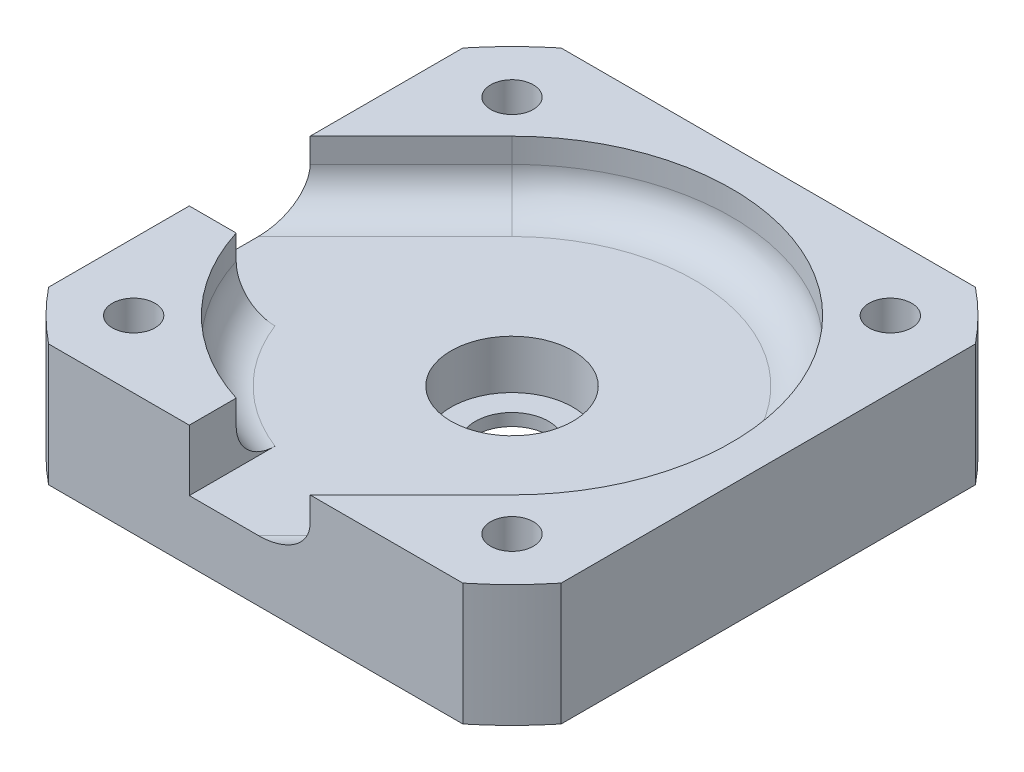
SolidWorks part; units mm, degrees
ref_plane "Front Plane" through (0, 0, 0) normal (0, 0, 1) x (1, 0, 0)
ref_plane "Top Plane" through (0, 0, 0) normal (0, 1, 0) x (1, 0, 0)
ref_plane "Right Plane" through (0, 0, 0) normal (1, 0, 0) x (0, 0, -1)
sketch "Sketch2" plane through (0, 0, 0) normal (0, 1, 0) x (1, 0, 0)
  line L1 (-21, 21) -> (21, 21)
  line L2 (-21, 21) -> (-21, -21)
  line L3 (-21, -21) -> (21, -21)
  line L4 (21, 21) -> (21, -21)
  line L5 (-21, 21) -> (21, -21) construction
  line L6 (-21, -21) -> (21, 21) construction
  point P0 (0, 0)
  dimension "D1" = 42
extrude "Boss-Extrude1" add sketch "Sketch2" along normal blind 10
sketch "Sketch3" plane through (0, 10, 0) normal (0, 1, 0) x (1, 0, 0)
  circle A0 centre (0, 0) radius 3
  dimension "D1" = 6
extrude "Cut-Extrude1" cut sketch "Sketch3" against normal through all
sketch "Sketch4" plane through (0, 10, 0) normal (0, 1, 0) x (1, 0, 0)
  line L1 (-15.5, 15.5) -> (15.5, 15.5) construction
  line L2 (-15.5, 15.5) -> (-15.5, -15.5) construction
  line L3 (-15.5, -15.5) -> (15.5, -15.5) construction
  line L4 (15.5, 15.5) -> (15.5, -15.5) construction
  line L5 (-15.5, 15.5) -> (15.5, -15.5) construction
  line L6 (-15.5, -15.5) -> (15.5, 15.5) construction
  circle A0 centre (-15.5, 15.5) radius 1.75
  circle A1 centre (15.5, 15.5) radius 1.75
  circle A2 centre (15.5, -15.5) radius 1.75
  circle A3 centre (-15.5, -15.5) radius 1.75
  point P0 (0, 0)
  point P16 (0, 0)
  dimension "D3" = 3.5
  dimension "D1" = 31
  dimension "D2" = 31
  dimension "D4" = 4
extrude "Cut-Extrude2" cut sketch "Sketch4" against normal through all
sketch "Sketch5" plane through (0, 10, 0) normal (0, 1, 0) x (1, 0, 0)
  circle A0 centre (0, 0) radius 27
  circle A1 centre (0, 0) radius 29.6985
  dimension "D1" = 54
extrude "Cut-Extrude4" cut sketch "Sketch5" against normal through all
sketch "Sketch6" plane through (0, 10, 0) normal (0, 1, 0) x (1, 0, 0)
  line L0 (-21, 4.4558) -> (-12.7279, 12.7279)
  line L1 (12.7279, -12.7279) -> (4.4558, -21)
  line L9 (-21, 16.9706) -> (-21, -16.9706) construction
  line L10 (-16.9706, -21) -> (16.9706, -21) construction
  line L11 (-7.7782, 7.7782) -> (-21, -5.4437) construction
  line L12 (4.4558, 21) -> (21, 4.4558) construction
  line L13 (7.5251, 21) -> (21, 7.5251) construction
  line L14 (16.9706, 21) -> (-16.9706, 21) construction
  line L15 (21, -16.9706) -> (21, 16.9706) construction
  line L18 (7.7782, -7.7782) -> (-5.4437, -21) construction
  line L19 (-21, 4.4558) -> (-21, -5.4437)
  line L21 (-5.4437, -17.1571) -> (-5.4437, -21)
  line L22 (-5.4437, -21) -> (4.4558, -21)
  line L23 (-17.1571, -5.4437) -> (-21, -5.4437)
  arc A0 (-12.7279, 12.7279) -> (12.7279, -12.7279) centre (0, 0) cw
  arc A2 (-17.1571, -5.4437) -> (-5.4437, -17.1571) centre (0, 0) ccw
  circle A3 centre (0, 0) radius 11 construction
  circle A5 centre (15.5, 15.5) radius 1.75 construction
  arc A6 (12.7279, -12.7279) -> (-12.7279, 12.7279) centre (0, 0) ccw
  point P14 (-15.9797, -5.4437)
  point P15 (-6.5354, -5.4437)
  point P24 (0.274, 0)
  point P25 (0, 0)
  point P28 (-5.4437, -13.4496)
  circle M13 centre (0, 0) radius 3
  line M14 (-16.9706, -21) -> (16.9706, -21)
  line M20 (-21, 16.9706) -> (-21, -16.9706)
  dimension "D1" = 45
  dimension "D3" = 18
  dimension "D5" = 22
  dimension "D2" = 45
  dimension "D4" = 45
extrude "Cut-Extrude5" cut sketch "Sketch6" against normal offset from surface (5 mm away) 5 contours L23 A2 L21 L1 A0 L0 M14 M20 M13 region at (-16.474, 10, -8.2019) up to face at (-15.5, 0, 17.25)
chamfer "Chamfer1" distance 1.8 angle 45 4 edges at (15.5, 0, -13.75) (-15.5, 0, -13.75) (-15.5, 0, 17.25) (15.5, 0, 17.25)
sketch "Sketch7" plane through (0, 5, 0) normal (0, 1, 0) x (1, 0, 0)
  circle A0 centre (0, 0) radius 5
  dimension "D1" = 10
extrude "Cut-Extrude6" cut sketch "Sketch7" against normal blind 4
fillet "Fillet1" radius 3 3 edges at (8.5919, 5, 16.864) (-16.864, 5, -8.5919) (12.7279, 5, -12.7279)
fillet "Fillet2" radius 3 1 edges at (-12.7279, 5, 12.7279)
